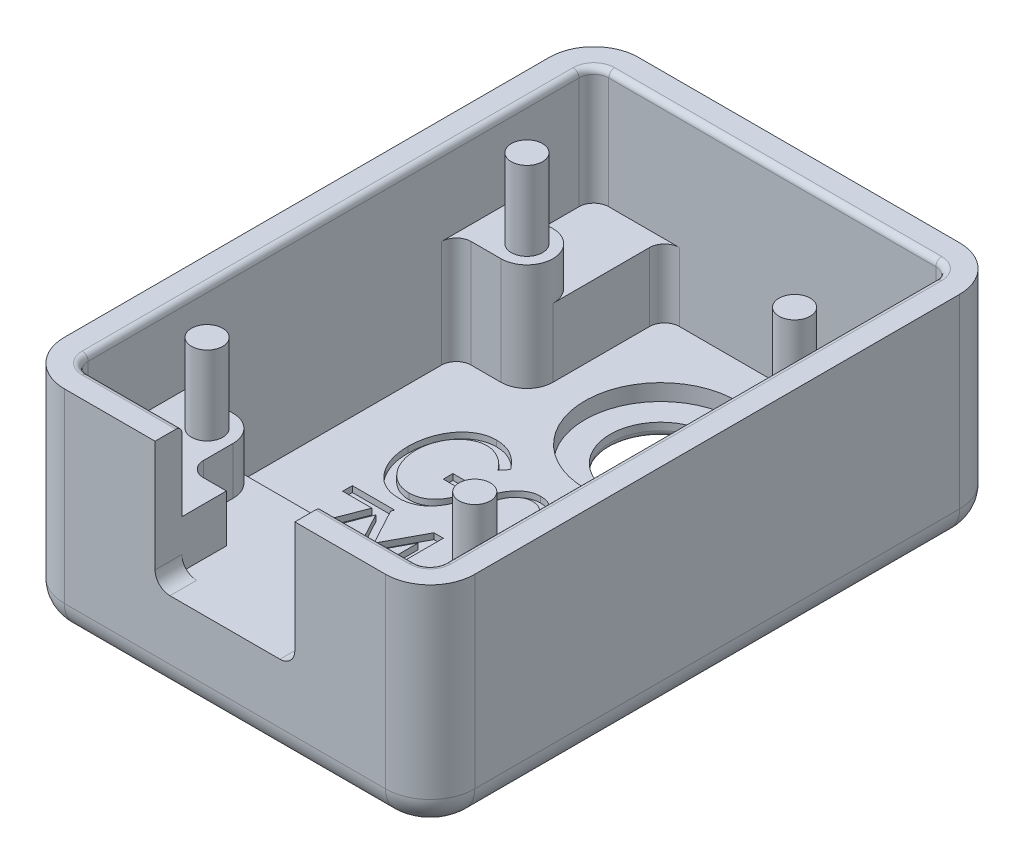
SolidWorks part; units mm, degrees
material "ABS PC"
ref_plane "Front" through (0, 0, 0) normal (0, 0, 1) x (1, 0, 0)
ref_plane "Top" through (0, 0, 0) normal (0, 1, 0) x (1, 0, 0)
ref_plane "Right" through (0, 0, 0) normal (1, 0, 0) x (0, 0, -1)
sketch "草图1" plane through (0, 0, 0) normal (0, 1, 0) x (1, 0, 0)
  line L0 (-9, 10.755) -> (9, -10.755) construction
  line L1 (-12, 18.255) -> (-12, -16.755)
  line L2 (-12, -16.755) -> (12, -16.755)
  line L3 (12, -16.755) -> (12, 18.255)
  line L4 (12, 18.255) -> (-12, 18.255)
  line L5 (-9, 12.505) -> (-11, 12.505)
  line L6 (-9, 9.005) -> (-11, 9.005)
  line L7 (9, 12.505) -> (11, 12.505)
  line L8 (9, 9.005) -> (11, 9.005)
  line L9 (-9, -9.005) -> (-11, -9.005)
  line L10 (9, -9.005) -> (11, -9.005)
  line L11 (-12, -13.755) -> (-4.7, -13.755)
  line L12 (-4.7, -13.755) -> (-4.7, -16.755)
  line L13 (12, -13.755) -> (4.7, -13.755)
  line L14 (4.7, -13.755) -> (4.7, -16.755)
  line L15 (-7.25, -10.755) -> (-7.25, -12.755)
  line L16 (7.25, -10.755) -> (7.25, -12.755)
  line L17 (-13.8, 20.055) -> (-13.8, -18.555)
  line L18 (-13.8, -18.555) -> (13.8, -18.555)
  line L19 (13.8, -18.555) -> (13.8, 20.055)
  line L20 (13.8, 20.055) -> (-13.8, 20.055)
  line L21 (9, -9.005) -> (-9, -9.005)
  circle A0 centre (-9, 10.755) radius 1.05
  circle A1 centre (-9, -10.755) radius 1.05
  circle A2 centre (9, -10.755) radius 1.05
  circle A3 centre (9, 10.755) radius 1.05
  circle A4 centre (-9, 10.755) radius 1.75
  circle A5 centre (9, 10.755) radius 1.75
  circle A6 centre (9, -10.755) radius 1.75
  circle A7 centre (-9, -10.755) radius 1.75
  arc A8 (-11, 9.005) -> (-12, 8.005) centre (-11, 8.005) ccw
  arc A9 (-11, 12.505) -> (-12, 13.505) centre (-11, 13.505) cw
  arc A10 (11, 9.005) -> (12, 8.005) centre (11, 8.005) cw
  arc A11 (11, 12.505) -> (12, 13.505) centre (11, 13.505) ccw
  arc A12 (11, -9.005) -> (12, -8.005) centre (11, -8.005) ccw
  arc A13 (-11, -9.005) -> (-12, -8.005) centre (-11, -8.005) cw
  arc A14 (-7.25, -12.755) -> (-6.25, -13.755) centre (-6.25, -12.755) ccw
  arc A15 (7.25, -12.755) -> (6.25, -13.755) centre (6.25, -12.755) cw
  arc A16 (-12, 17.255) -> (-11, 18.255) centre (-11, 17.255) cw
  arc A17 (11, 18.255) -> (12, 17.255) centre (11, 17.255) cw
  arc A18 (-12, -15.755) -> (-11, -16.755) centre (-11, -15.755) ccw
  arc A19 (12, -15.755) -> (11, -16.755) centre (11, -15.755) cw
  point P9 (0, 0)
  point P47 (0, -16.755)
  dimension "D1" = 2.1
  dimension "D4" = 3.5
  dimension "D9" = 1
  dimension "D10" = 3
  dimension "D13" = 1.8
  dimension "D2" = 18
  dimension "D3" = 21.51
  dimension "D5" = 3
  dimension "D6" = 3
  dimension "D7" = 6
  dimension "D8" = 7.5
  dimension "D11" = 4.7
  dimension "D12" = 4.7
extrude "凸台-拉伸2" add sketch "草图1<3>" along normal blind 5.3 separate body contours L19 L20 L17 L18 L4 L3 L2 L1 | L1 A16 L4 | L4 A17 L3 | A18 L1 L2 | L3 A19 L2 | A1 | A2 | A0 | A3 region at (-11.7766, 0, -18.0316) region at (11.7766, 0, -18.0316) region at (-11.7766, 0, 16.5316) region at (11.7766, 0, 16.5316) region at (0, 0, -19.5804) region at (-9, 0, -10.755) region at (-9, 0, 10.755) region at (9, 0, 10.755) region at (9, 0, -10.755)
sketch "草图1<3>" plane through (0, 0, 0) normal (0, 1, 0) x (1, 0, 0) same geometry as "草图1"
extrude "凸台-拉伸3" add sketch "草图1" against normal blind 7.2 contours A14 L15 A7 L9 A13 L1 L11 | L12 L11 L1 L2 | L13 L14 L2 L3 | A7 A1 | L5 A9 L1 A8 L6 A4 | A0 A4 | A11 L7 A5 L8 A10 L3 | A5 A3 | L16 A15 L13 L3 A12 L10 A6 | A6 A2 | L19 L20 L17 L18 L4 L3 L2 L1 | L1 A16 L4 | L4 A17 L3 | L3 A19 L2 | A18 L1 L2 | A1 | A0 | A3 | A2 region at (-11.7766, 0, -18.0316) region at (-11.1849, 0, -10.755) region at (11.7766, 0, -18.0316) region at (-11.7646, 0, 8.7696) region at (-7.7976, 0, -11.9574) region at (11.1849, 0, -10.755) region at (-8.3161, 0, 15.2424) region at (-11.7766, 0, 16.5316) region at (-7.7976, 0, 9.5526) region at (11.9187, 0, 10.88) region at (10.2024, 0, -11.9574) region at (10.2024, 0, 9.5526) region at (8.3161, 0, 15.2424) region at (11.7766, 0, 16.5316) region at (0, 0, -19.5804) region at (-9, 0, -10.755) region at (-9, 0, 10.755) region at (9, 0, 10.755) region at (9, 0, -10.755)
extrude "凸台-拉伸4" add sketch "草图1<5>" against normal blind 4.9 from offset 3.2 contours A15 L16 L15 A14 L11 L12 L2 L14 L13 | L21 L0 A6 region at (8.0249, 0, 9.1298) region at (-0.0176, 0, 12.4668) offset against normal yes
sketch "草图1<5>" plane through (0, 0, 0) normal (0, 1, 0) x (1, 0, 0) same geometry as "草图1"
sketch "草图2" plane through (0, 0, 18.555) normal (0, 0, 1) x (1, 0, 0)
  line L0 (0, -0.9196) -> (0, 2.5902) construction
  line L1 (-4.7, -3.2) -> (-4.7, 5.3)
  line L3 (-13.8, 5.3) -> (13.8, 5.3) construction
  line L5 (-4.7, 5.3) -> (4.7, 5.3)
  line L6 (4.7, 5.3) -> (4.7, -3.2)
  line L9 (-4.7, -3.2) -> (4.7, -3.2) construction
  line L10 (-4.7, -3.2) -> (4.7, -3.2)
  arc A0 (4.7, -2.2) -> (3.7, -3.2) centre (3.7, -2.2) cw
  arc A1 (-4.7, -2.2) -> (-3.7, -3.2) centre (-3.7, -2.2) ccw
  point P4 (0, -3.2)
  line M8 (13.8, 5.3) -> (-13.8, 5.3)
  dimension "D1" = 4.7
  dimension "D3" = 1
  dimension "D2" = 4.7
extrude "切除-拉伸1" cut sketch "草图2" against normal blind 2.3 contours L1 L10 L6 M8 region at (0, 1.0717, 18.555)
extrude "凸台-拉伸5" add sketch "草图1<6>" against normal blind 2 from offset 7.2 contours A4 L0 L21 L10 A12 L3 A10 L8 A5 L7 A11 A17 L4 A16 L1 A9 L5 | L0 A4 L6 A8 L1 A13 L9 L21 | L1 A16 L4 | L19 L20 L17 L18 L4 L3 L2 L1 | L4 A17 L3 | L5 A9 L1 A8 L6 A4 | A0 A4 | A11 L7 A5 L8 A10 L3 | A5 A3 | L0 L21 A7 L15 A14 L11 L12 L2 L14 L13 A15 L16 A6 | L12 L11 L1 L2 | A14 L15 A7 L9 A13 L1 L11 | A7 A1 | L16 A15 L13 L3 A12 L10 A6 | L13 L14 L2 L3 | L21 L0 A6 | A6 A2 | A18 L1 L2 | L3 A19 L2 | A1 | A2 | A0 | A3 region at (-8.4195, 0, -9.1567) region at (2.7659, 0, -7.6078) region at (-5.2011, 0, 1.8777) region at (-9.9244, 0, -11.1868) region at (8.0249, 0, 9.1298) region at (-0.0176, 0, 12.4668) region at (-11.1849, 0, -10.755) region at (9.4318, 0, 9.8306) region at (8.4195, 0, 9.1567) region at (10, 0, 9.0863) region at (-10.2949, 0, 12.0499) region at (-7.7976, 0, 9.5526) region at (8.3161, 0, 15.2424) region at (11.1849, 0, -10.755) region at (-8.3161, 0, 15.2424) region at (-11.7766, 0, -18.0316) region at (11.7766, 0, 16.5316) region at (-11.7766, 0, 16.5316) region at (11.7766, 0, -18.0316) region at (7.2995, 0, -10.755) region at (0, 0, -19.5804) region at (-9, 0, 10.755) region at (9, 0, -10.755) offset against normal yes
sketch "草图1<6>" plane through (0, 0, 0) normal (0, 1, 0) x (1, 0, 0) same geometry as "草图1"
sketch "草图3" plane through (0, -7.2, 0) normal (0, 1, 0) x (1, 0, 0)
  line L0 (-11, 18.255) -> (-6.25, 18.255)
  line L2 (-9, 12.505) -> (-11, 12.505) construction
  line L3 (-9, 12.505) -> (-11, 12.505)
  line L4 (-12, 17.255) -> (-12, 13.505) construction
  line L5 (-12, 17.255) -> (-12, 13.505)
  line L6 (6.25, 18.255) -> (11, 18.255)
  line L7 (7.25, 17.255) -> (7.25, 10.755)
  line L8 (12, 13.505) -> (12, 17.255) construction
  line L9 (12, 13.505) -> (12, 17.255)
  line L10 (9, 12.505) -> (11, 12.505) construction
  line L11 (9, 12.505) -> (11, 12.505)
  line L14 (-7.25, 17.255) -> (-7.25, 10.755)
  line L15 (-7.25, 10.755) -> (7.25, 10.755) construction
  line L16 (0, 18.255) -> (0, 10.755) construction
  line L17 (11, 18.255) -> (-11, 18.255) construction
  arc A0 (-9, 9.005) -> (-9, 12.505) centre (-9, 10.755) ccw construction
  arc A1 (-9, 9.005) -> (-9, 12.505) centre (-9, 10.755) ccw
  arc A2 (-12, 13.505) -> (-11, 12.505) centre (-11, 13.505) ccw construction
  arc A3 (-12, 13.505) -> (-11, 12.505) centre (-11, 13.505) ccw
  arc A4 (-11, 18.255) -> (-12, 17.255) centre (-11, 17.255) ccw construction
  arc A5 (-11, 18.255) -> (-12, 17.255) centre (-11, 17.255) ccw
  arc A6 (9, 12.505) -> (9, 9.005) centre (9, 10.755) ccw construction
  arc A7 (9, 12.505) -> (9, 9.005) centre (9, 10.755) ccw
  arc A8 (12, 17.255) -> (11, 18.255) centre (11, 17.255) ccw construction
  arc A9 (12, 17.255) -> (11, 18.255) centre (11, 17.255) ccw
  arc A10 (11, 12.505) -> (12, 13.505) centre (11, 13.505) ccw construction
  arc A11 (11, 12.505) -> (12, 13.505) centre (11, 13.505) ccw
  arc A12 (-6.25, 18.255) -> (-7.25, 17.255) centre (-6.25, 17.255) ccw
  arc A13 (6.25, 18.255) -> (7.25, 17.255) centre (6.25, 17.255) cw
  circle A14 centre (0, 10.755) radius 3.4
  circle A15 centre (0, 10.755) radius 5.1
  line M2 (9, 12.505) -> (11, 12.505)
  arc M3 (11, 12.505) -> (12, 13.505) centre (11, 13.505) ccw
  line M4 (12, 13.505) -> (12, 17.255)
  arc M5 (12, 17.255) -> (11, 18.255) centre (11, 17.255) ccw
  line M6 (11, 18.255) -> (-11, 18.255)
  arc M7 (-11, 18.255) -> (-12, 17.255) centre (-11, 17.255) ccw
  line M8 (-12, 17.255) -> (-12, 13.505)
  arc M9 (-12, 13.505) -> (-11, 12.505) centre (-11, 13.505) ccw
  line M10 (-11, 12.505) -> (-9, 12.505)
  arc M11 (-9, 12.505) -> (-9, 9.005) centre (-9, 10.755) cw
  arc M21 (9, 9.005) -> (9, 12.505) centre (9, 10.755) cw
  dimension "D1" = 1
  dimension "D2" = 1
  dimension "D3" = 10.2
  dimension "D4" = 6.8
extrude "凸台-拉伸6" add sketch "草图3" along normal blind 4.6 contours A12 L14 M6 M7 M8 M9 M10 M11 | A13 L7 M6 M21 M2 M3 M4 M5 region at (9.5247, -7.2, -15.3232) region at (-9.5247, -7.2, -15.3232)
fillet "圆角1" radius 3 4 edges at (-13.8, -1.95, -20.055) (13.8, -1.95, -20.055) (13.8, -1.95, 18.555) (-13.8, -1.95, 18.555)
fillet "圆角3" radius 2 8 edges at (12.9213, -9.2, 17.6763) (0, -9.2, 18.555) (-12.9213, -9.2, 17.6763) (-13.8, -9.2, -0.75) (-12.9213, -9.2, -19.1763) (0, -9.2, -20.055) (12.9213, -9.2, -19.1763) (13.8, -9.2, -0.75)
extrude "切除-拉伸2" cut sketch "草图3<7>" against normal blind 3 contours A14 region at (0, -7.2, -10.755)
sketch "草图3<7>" plane through (0, -7.2, 0) normal (0, 1, 0) x (1, 0, 0) same geometry as "草图3"
extrude "切除-拉伸3" cut sketch "草图3<8>" against normal blind 1.1 contours A15 A14 region at (-4.9558, -7.2, -10.755)
sketch "草图3<8>" plane through (0, -7.2, 0) normal (0, 1, 0) x (1, 0, 0) same geometry as "草图3"
fillet "圆角4" radius 0.4 1 edges at (0, -9.2, -7.355)
fillet "圆角5" radius 0.4 9 edges at (-11.7071, 5.3, -17.9621) (0, 5.3, -18.255) (11.7071, 5.3, -17.9621) (12, 5.3, -0.75) (11.7071, 5.3, 16.4621) (-7.85, 5.3, 16.755) (7.85, 5.3, 16.755) (-11.7071, 5.3, 16.4621) (-12, 5.3, -0.75)
sketch "草图4" plane through (0, -7.2, 0) normal (0, 1, 0) x (1, 0, 0)
  text T0 "GaAs" font "Century Gothic" height 6.35
extrude "切除-拉伸4" cut sketch "草图4" against normal blind 0.4
sketch "草图5" plane through (0, -7.2, 0) normal (0, 1, 0) x (1, 0, 0)
  text T0 "ZYH    2" font "Century Gothic" height 6.35
extrude "切除-拉伸5" cut sketch "草图5" against normal blind 0.4
